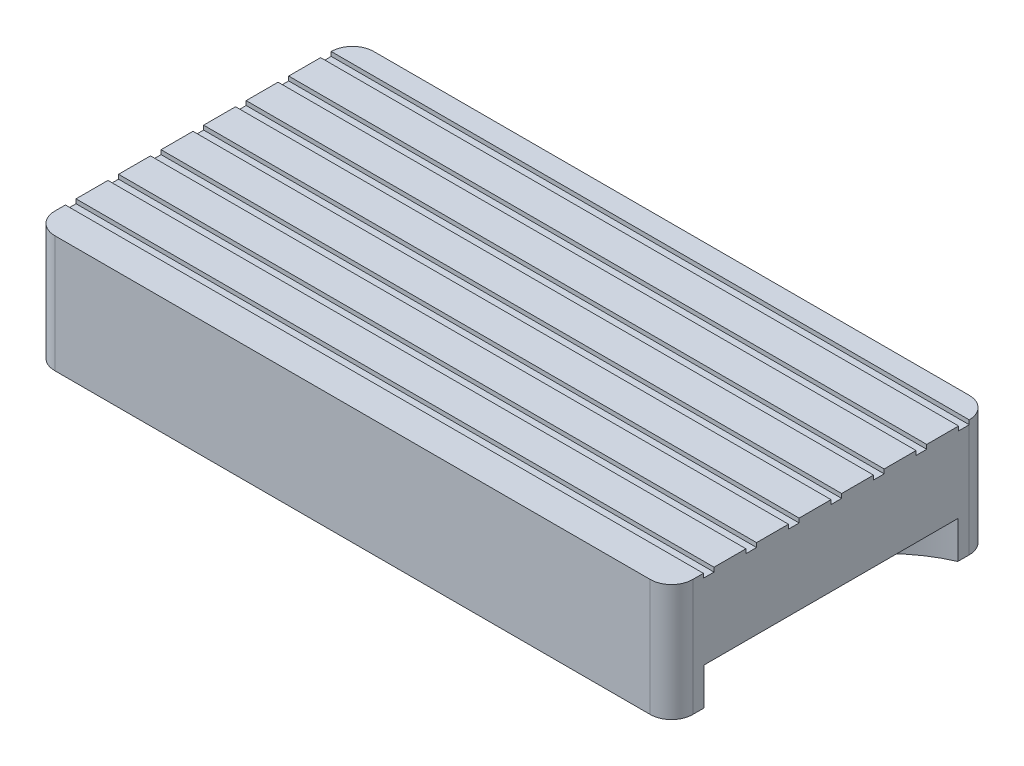
SolidWorks part; units mm, degrees
material "Copper"
ref_plane "Front Plane" through (0, 0, 0) normal (0, 0, 1) x (1, 0, 0)
ref_plane "Top Plane" through (0, 0, 0) normal (0, 1, 0) x (1, 0, 0)
ref_plane "Right Plane" through (0, 0, 0) normal (1, 0, 0) x (0, 0, -1)
sketch "Sketch1" plane through (0, 0, 0) normal (0, 1, 0) x (1, 0, 0)
  line L0 (-15, 0) -> (0, 0) construction
  line L1 (-15, -7.5) -> (15, -7.5)
  line L2 (-15, -7.5) -> (-15, 7.5)
  line L3 (-15, 7.5) -> (15, 7.5)
  line L4 (15, -7.5) -> (15, 7.5)
  line L5 (0, 0) -> (0, -7.5) construction
  dimension "D1" = 15
  dimension "D2" = 30
extrude "Boss-Extrude1" add sketch "Sketch1" along normal blind 5.5
sketch "Sketch2" plane through (0, 0, 0) normal (1, 0, 0) x (0, 0, -1)
  line L0 (-7.5, 5.5) -> (7.5, 5.5) construction
  line L1 (-6, 5.5) -> (-5.5, 5.5)
  line L2 (-6, 5.5) -> (-6, 5.3)
  line L3 (-6, 5.3) -> (-5.5, 5.3)
  line L4 (-5.5, 5.5) -> (-5.5, 5.3)
  line L5 (-7.5, 5.5) -> (-7.5, 0) construction
  line L6 (-3.5, 5.5) -> (-3.5, 5.3)
  line L7 (-4, 5.5) -> (-3.5, 5.5)
  line L8 (-4, 5.5) -> (-4, 5.3)
  line L9 (-4, 5.3) -> (-3.5, 5.3)
  line L10 (-1.5, 5.5) -> (-1.5, 5.3)
  line L11 (-2, 5.5) -> (-1.5, 5.5)
  line L12 (-2, 5.5) -> (-2, 5.3)
  line L13 (-2, 5.3) -> (-1.5, 5.3)
  line L14 (0.5, 5.5) -> (0.5, 5.3)
  line L15 (0, 5.5) -> (0.5, 5.5)
  line L16 (0, 5.5) -> (0, 5.3)
  line L17 (0, 5.3) -> (0.5, 5.3)
  line L18 (2.5, 5.5) -> (2.5, 5.3)
  line L19 (2, 5.5) -> (2.5, 5.5)
  line L20 (2, 5.5) -> (2, 5.3)
  line L21 (2, 5.3) -> (2.5, 5.3)
  line L22 (4.5, 5.5) -> (4.5, 5.3)
  line L23 (4, 5.5) -> (4.5, 5.5)
  line L24 (4, 5.5) -> (4, 5.3)
  line L25 (4, 5.3) -> (4.5, 5.3)
  line L26 (6.5, 5.5) -> (6.5, 5.3)
  line L27 (6, 5.5) -> (6.5, 5.5)
  line L28 (6, 5.5) -> (6, 5.3)
  line L29 (6, 5.3) -> (6.5, 5.3)
  dimension "D1" = 0.2
  dimension "D2" = 0.5
  dimension "D3" = 1.5
  dimension "D5" = 1.5
  dimension "D4" = 7
extrude "Cut-Extrude2" cut sketch "Sketch2" against normal through all both and the other way through all
ref_plane "Plane1" through (0, 0, 4) normal (0, 0, 1) x (1, 0, 0)
sketch "Sketch8" plane through (0, 0, 4) normal (0, 0, 1) x (1, 0, 0)
  line L0 (10.25, 0) -> (10.25, 3)
  line L1 (-15, 0) -> (15, 0) construction
  line L2 (10.25, 3) -> (9, 3.7217)
  line L3 (9, 3.7217) -> (9, 0)
  line L4 (9, 0) -> (10.25, 0)
  line L5 (0, 0) -> (0, 7.2512) construction
  line L6 (9, 0) -> (9, 5.5) construction
  line L7 (-15, 5.5) -> (15, 5.5) construction
  dimension "D1" = 18
  dimension "D2" = 2.5
  dimension "D3" = 3
  dimension "D4" = 60
revolve "Cut-Revolve1" cut sketch "Sketch8" angle 360 about L6
mirror "Mirror1" about plane through (0, 0, 0) normal (0, 0, 1) of "Cut-Revolve1"
mirror "Mirror2" about plane through (0, 0, 0) normal (1, 0, 0) of "Mirror1"
sketch "Sketch5" plane through (-15, 0, 0) normal (1, 0, 0) x (0, 0, -1)
  line L0 (-7.5, 0) -> (7.5, 0) construction
  line L1 (4.1, 0) -> (-5.1, 0)
  line L2 (4.1, 0) -> (4.1, 5.5)
  line L3 (4.1, 5.5) -> (-5.1, 5.5)
  line L4 (-5.1, 0) -> (-5.1, 5.5)
  line L5 (-3.5, 5.5) -> (-2, 5.5) construction
  line L6 (7.5, 0) -> (-7.5, 0) construction
  line L7 (-0.5, 0) -> (-0.5, 5.5) construction
  dimension "D1" = 9.2
  dimension "D2" = 0.5
extrude "Cut-Extrude4" [suppressed] cut sketch "Sketch5" along normal blind 1.6
sketch "Sketch9" plane through (0, 0, 0) normal (0, 0, 1) x (1, 0, 0)
  line L0 (-15, 2.5) -> (-7.6783, 2.5)
  line L1 (-15, 5.5) -> (-15, 0) construction
  line L2 (-7.6783, 2.5) -> (-8.4, 3.75)
  line L3 (-8.4, 3.75) -> (-15, 3.75)
  line L4 (-15, 3.75) -> (-15, 2.5)
  line L5 (-15, 2.5) -> (-16.9854, 2.5) construction
  line L6 (15, 0) -> (-15, 0) construction
  dimension "D1" = 2.5
  dimension "D2" = 6.6
  dimension "D3" = 60
  dimension "D4" = 2.5
revolve "Cut-Revolve2" cut sketch "Sketch9" angle 360 about L5
sketch "Sketch7" plane through (0, 0, 0) normal (0, -1, 0) x (1, 0, 0)
  line L0 (17.59, 0) -> (0, 0) construction
  circle A0 centre (17.59, 0) radius 6.5
  dimension "D1" = 13
  dimension "D2" = 17.59
extrude "Cut-Extrude6" cut sketch "Sketch7" against normal blind 1.75
fillet "Fillet1" radius 1 4 edges at (-15, 2.75, 7.5) (-15, 2.75, -7.5) (15, 2.75, -7.5) (15, 2.75, 7.5)
